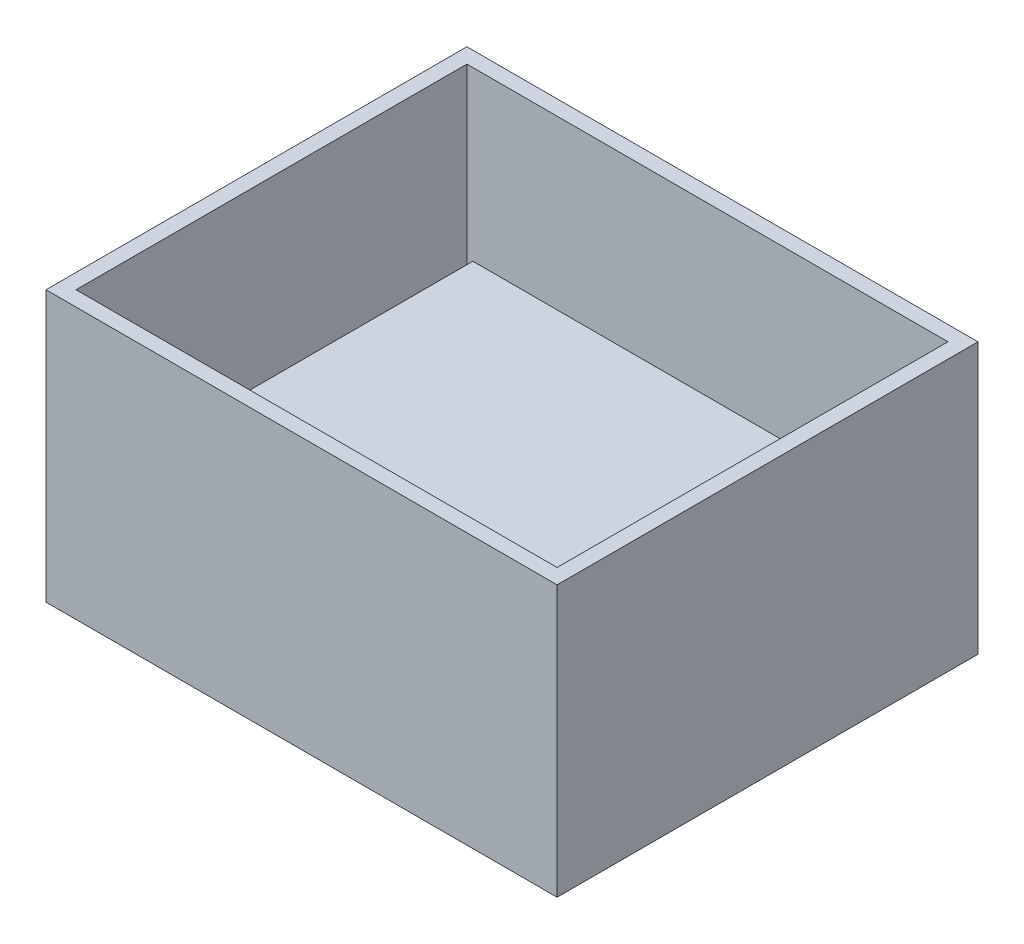
SolidWorks part; units mm, degrees
ref_plane "Front Plane" through (0, 0, 0) normal (0, 0, 1) x (1, 0, 0)
ref_plane "Top Plane" through (0, 0, 0) normal (0, 1, 0) x (1, 0, 0)
ref_plane "Right Plane" through (0, 0, 0) normal (1, 0, 0) x (0, 0, -1)
other "Configuration Table"
sketch "Sketch1" plane through (0, 0, 0) normal (1, 0, 0) x (0, 0, -1)
  line L1 (-45, 0) -> (-115, 0)
  line L2 (-45, 0) -> (-45, 45)
  line L3 (-45, 45) -> (-115, 45)
  line L4 (-115, 0) -> (-115, 45)
  line L5 (-45, 0) -> (-115, 45) construction
  line L6 (-45, 45) -> (-115, 0) construction
extrude "enclosure" add sketch "Sketch1" along normal blind 85 from offset 165 separate body
sketch "Sketch2" plane through (0, 0, 0) normal (1, 0, 0) x (0, 0, -1)
  line L1 (-47.5, 2.5) -> (-112.5, 2.5)
  line L2 (-47.5, 2.5) -> (-47.5, 50)
  line L3 (-47.5, 50) -> (-112.5, 50)
  line L4 (-112.5, 2.5) -> (-112.5, 50)
  line L5 (-47.5, 2.5) -> (-112.5, 50) construction
  line L6 (-47.5, 50) -> (-112.5, 2.5) construction
extrude "cavity" add sketch "Sketch2" along normal blind 80 from offset 167.5 separate body
combine bodies "Combine1" operation type subtract main body 102 bodies to subtract 103
sketch "Sketch3" plane through (0, 0, 0) normal (1, 0, 0) x (0, 0, -1)
  line L1 (-52, 6) -> (-105.4, 6)
  line L2 (-52, 6) -> (-52, 7.6)
  line L3 (-52, 7.6) -> (-105.4, 7.6)
  line L4 (-105.4, 6) -> (-105.4, 7.6)
  line L5 (-52, 6) -> (-105.4, 7.6) construction
  line L6 (-52, 7.6) -> (-105.4, 6) construction
extrude "arduino_uno" add sketch "Sketch3" along normal blind 68.6 from offset 173 separate body
sketch "Sketch4" plane through (0, 0, 0) normal (1, 0, 0) x (0, 0, -1)
  line L1 (-52, 20) -> (-105.4, 20)
  line L2 (-52, 20) -> (-52, 21.6)
  line L3 (-52, 21.6) -> (-105.4, 21.6)
  line L4 (-105.4, 20) -> (-105.4, 21.6)
  line L5 (-52, 20) -> (-105.4, 21.6) construction
  line L6 (-52, 21.6) -> (-105.4, 20) construction
extrude "sensor_shield" add sketch "Sketch4" along normal blind 68.6 from offset 173 separate body
